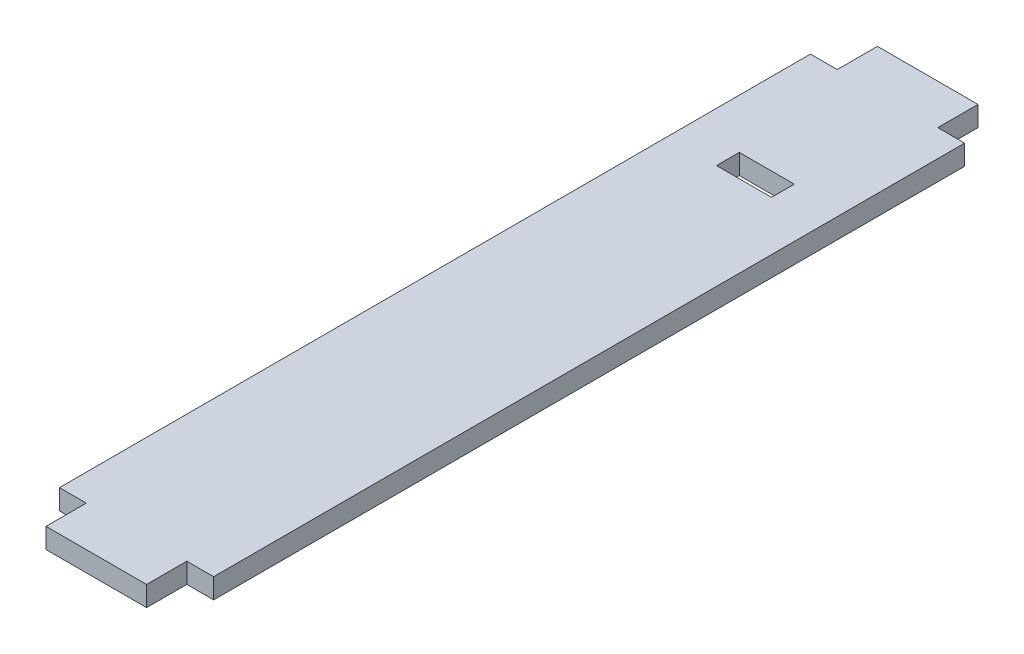
SolidWorks part; units mm, degrees
material "AISI 304"
ref_plane "Front Plane" through (0, 0, 0) normal (0, 0, 1) x (1, 0, 0)
ref_plane "Top Plane" through (0, 0, 0) normal (0, 1, 0) x (1, 0, 0)
ref_plane "Right Plane" through (0, 0, 0) normal (1, 0, 0) x (0, 0, -1)
sketch "Sketch1" plane through (0, 0, 0) normal (0, 1, 0) x (1, 0, 0)
  line L0 (3.75, 28) -> (5.75, 28)
  line L1 (-5.75, -28) -> (-3.75, -28)
  line L2 (-5.75, -28) -> (-5.75, -16.6)
  line L3 (-5.75, 28) -> (-3.75, 28)
  line L4 (5.75, -28) -> (5.75, -14.1)
  line L5 (-5.75, -28) -> (5.75, 28) construction
  line L6 (-5.75, 28) -> (5.75, -28) construction
  line L8 (3.75, 28) -> (3.75, 31)
  line L9 (3.75, 31) -> (-3.75, 31)
  line L10 (-3.75, 28) -> (-3.75, 31)
  line L12 (-3.75, -28) -> (-3.75, -31)
  line L13 (-3.75, -31) -> (3.75, -31)
  line L14 (3.75, -28) -> (3.75, -31)
  line L15 (3.75, -28) -> (5.75, -28)
  line L16 (-5.75, -14.9) -> (-5.75, 28)
  line L21 (5.75, -12.4) -> (5.75, 28)
  line L26 (0, 0) -> (0, 53.4412) construction
  line L31 (-5.75, -16.6) -> (-5.75, -14.9)
  line L32 (-2.05, 17.3) -> (2.05, 17.3)
  line L33 (-2.05, 17.3) -> (-2.05, 19)
  line L34 (-2.05, 19) -> (2.05, 19)
  line L35 (2.05, 17.3) -> (2.05, 19)
  line L36 (-2.05, 17.3) -> (2.05, 19) construction
  line L37 (-2.05, 19) -> (2.05, 17.3) construction
  line L38 (5.75, -12.4) -> (5.75, -14.1)
  point P0 (0, 0)
  point P23 (0, 18.15)
  dimension "D1" = 7.5
  dimension "D2" = 2
  dimension "D3" = 2
  dimension "D4" = 3
  dimension "D5" = 2
  dimension "D6" = 2
  dimension "D7" = 3
  dimension "D8" = 56
  dimension "D11" = 1.7
  dimension "D12" = 3.7
  dimension "D13" = 12
extrude "Boss-Extrude1" add sketch "Sketch1" along normal blind 1.5
